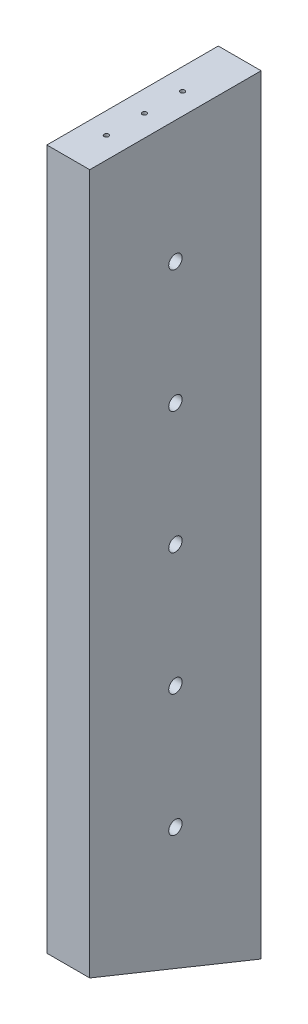
SolidWorks part; units mm, degrees
material "MDF"
ref_plane "Front" through (0, 0, 0) normal (0, 0, 1) x (1, 0, 0)
ref_plane "Top" through (0, 0, 0) normal (0, 1, 0) x (1, 0, 0)
ref_plane "Right" through (0, 0, 0) normal (1, 0, 0) x (0, 0, -1)
sketch "Sketch1" plane through (0, 0, 0) normal (0, 0, 1) x (1, 0, 0)
  line L0 (505.9785, 6983.73) -> (266.7, 6983.73) construction
  line L1 (494.5273, 6641.7419) -> (475.4773, 6641.7419)
  line L2 (494.5273, 6641.7419) -> (494.5273, 6983.73)
  line L3 (494.5273, 6983.73) -> (475.4773, 6983.73)
  line L4 (475.4773, 6641.7419) -> (475.4773, 6983.73)
  dimension "D1" = 19.05
extrude "Boss-Extrude1" add sketch "Sketch1" along normal blind 76.2
sketch "Sketch2" plane through (494.5273, 0, 0) normal (1, 0, 0) x (0, 0, -1)
  line L0 (0, 6641.7419) -> (-76.2, 6672.5287)
  line L1 (-76.2, 6641.7419) -> (-76.2, 6983.73) construction
  line L2 (-76.2, 6672.5287) -> (-76.2, 6641.7419)
  line L3 (-76.2, 6641.7419) -> (0, 6641.7419)
  line L5 (-110.6161, 6686.4337) -> (-134.1666, 6695.9487) construction
extrude "Cut-Extrude1" cut sketch "Sketch2" against normal up to next
hole_wizard "5/64 (0.07813) Diameter Hole1" positions "Sketch3" profile "Sketch4" hole size "5/64" standard "ANSI Inch"
sketch "Sketch3" plane through (0, 0, -19.05) normal (0, 0, -1) x (-1, 0, 0)
  point P0 (-481.5892, 6993.255)
  point P9 (-386.3392, 6993.255)
  point P18 (-291.0892, 6993.255)
  point P21 (-295.275, 6965.1359)
  point P33 (-295.275, 6812.7359)
  point P45 (-295.275, 6660.3359)
  point P48 (-285.1664, 6631.4688)
  point P66 (-475.4773, 6631.4688)
  point P69 (-485.0023, 6660.3359)
  point P81 (-485.0023, 6812.7359)
  point P93 (-485.0023, 6965.1359)
  point P96 (-478.3656, 6611.6708)
  point P114 (-287.8656, 6611.6708)
  point P117 (-307.975, 6564.3379)
  point P127 (-307.975, 6488.1379)
  point P130 (-284.9609, 6440.805)
  point P143 (-380.2109, 6440.805)
  point P152 (-475.4609, 6440.805)
  point P155 (-446.8313, 6488.1379)
  point P161 (-446.8313, 6564.3379)
  point P164 (-472.2313, 6396.355)
  point P170 (-472.2313, 6320.155)
  point P173 (-472.6532, 6275.705)
  point P182 (-377.4032, 6275.705)
  point P191 (-282.1532, 6275.705)
  point P194 (-282.575, 6320.155)
  point P200 (-282.575, 6396.355)
  point P203 (-435.5986, 6221.73)
  point P209 (-435.5986, 6145.53)
  point P233 (-450.5925, 6091.555)
  point P242 (-460.9986, 6091.5555)
  point P245 (-460.9986, 6056.63)
  point P251 (-460.9986, 5980.43)
  point P263 (-460.9986, 5945.505)
  point P280 (-282.1532, 5945.505)
  point P284 (-368.6118, 5945.505)
sketch "Sketch4" plane through (481.5892, 6993.255, -19.05) normal (1, 0, 0) x (0, 1, 0)
  line L0 (0, 0) -> (0, 38.6962)
  line L1 (0, 38.6962) -> (0.9923, 38.1)
  line L2 (0.9923, 38.1) -> (0.9923, 0)
  line L3 (0.9923, 0) -> (0, 0)
  line L4 (0, 38.6962) -> (-0.9923, 38.1) construction
  line L5 (0, -6.35) -> (0, 107.95) construction
  dimension "Hole Dia." = 1.9845
  dimension "Hole Depth" = 38.1
  dimension "Drill Angle" = 118
hole_wizard "5/64 (0.07813) Diameter Hole2" positions "Sketch5" profile "Sketch6" hole size "5/64" standard "ANSI Inch"
sketch "Sketch5" plane through (189.7273, 0, -19.05) normal (0, 0, -1) x (-1, 0, 0)
  point P0 (-481.5892, 6993.255)
  point P9 (-386.3392, 6993.255)
  point P18 (-291.0892, 6993.255)
  point P21 (-295.275, 6965.1359)
  point P33 (-295.275, 6812.7359)
  point P45 (-295.275, 6660.3359)
  point P48 (-285.1664, 6631.4688)
  point P66 (-475.4773, 6631.4688)
  point P69 (-485.0023, 6660.3359)
  point P81 (-485.0023, 6812.7359)
  point P93 (-485.0023, 6965.1359)
  point P96 (-478.3656, 6611.6708)
  point P114 (-287.8656, 6611.6708)
  point P117 (-307.975, 6564.3379)
  point P127 (-307.975, 6488.1379)
  point P130 (-284.9609, 6440.805)
  point P143 (-380.2109, 6440.805)
  point P152 (-475.4609, 6440.805)
  point P155 (-446.8313, 6488.1379)
  point P161 (-446.8313, 6564.3379)
  point P164 (-472.2313, 6396.355)
  point P170 (-472.2313, 6320.155)
  point P173 (-472.6532, 6275.705)
  point P182 (-377.4032, 6275.705)
  point P191 (-282.1532, 6275.705)
  point P194 (-282.575, 6320.155)
  point P200 (-282.575, 6396.355)
  point P203 (-435.5986, 6221.73)
  point P209 (-435.5986, 6145.53)
  point P233 (-450.5925, 6091.555)
  point P242 (-460.9986, 6091.5555)
  point P245 (-460.9986, 6056.63)
  point P251 (-460.9986, 5980.43)
  point P263 (-460.9986, 5945.505)
  point P280 (-282.1532, 5945.505)
  point P284 (-368.6118, 5945.505)
sketch "Sketch6" plane through (671.3166, 6993.255, -19.05) normal (1, 0, 0) x (0, 1, 0)
  line L0 (0, 0) -> (0, 38.6962)
  line L1 (0, 38.6962) -> (0.9923, 38.1)
  line L2 (0.9923, 38.1) -> (0.9923, 0)
  line L3 (0.9923, 0) -> (0, 0)
  line L4 (0, 38.6962) -> (-0.9923, 38.1) construction
  line L5 (0, -6.35) -> (0, 107.95) construction
  dimension "Hole Dia." = 1.9845
  dimension "Hole Depth" = 38.1
  dimension "Drill Angle" = 118
hole_wizard "5/64 (0.07813) Diameter Hole3" positions "Sketch7" profile "Sketch8" hole size "5/64" standard "ANSI Inch"
sketch "Sketch7" plane through (0, 6983.73, 0) normal (0, 1, 0) x (1, 0, 0)
  line L0 (485.0023, -76.2) -> (485.0023, 0) construction
  line L1 (494.5273, -76.2) -> (475.4773, -76.2) construction
  line L2 (494.5273, 0) -> (475.4773, 0) construction
  line L3 (485.0023, -25.4) -> (485.0023, -42.3333)
  line L4 (485.0023, -42.3333) -> (485.0023, -59.2667)
  line L5 (485.0023, -59.2667) -> (485.0023, -76.2)
  point P8 (485.0023, -25.4)
  point P10 (485.0023, -42.3333)
  point P12 (485.0023, -59.2667)
  dimension "D1" = 25.4
sketch "Sketch8" plane through (485.0023, 6983.73, 59.2667) normal (1, 0, 0) x (0, 0, 1)
  line L0 (0, 0) -> (0, 19.6462)
  line L1 (0, 19.6462) -> (0.9923, 19.05)
  line L2 (0.9923, 19.05) -> (0.9923, 0)
  line L5 (0.9923, 0) -> (0, 0)
  line L10 (0, 19.6462) -> (-0.9923, 19.05) construction
  line L11 (0, -6.35) -> (0, 107.95) construction
  dimension "Hole Dia." = 1.9845
  dimension "Hole Depth" = 19.05
  dimension "Drill Angle" = 118
hole_wizard "5/64 (0.07813) Diameter Hole4" positions "Sketch11" profile "Sketch10" hole size "5/64" standard "ANSI Inch"
sketch "Sketch11" plane through (0, 5709.7056, -2306.8708) normal (0, -0.9272, 0.3746) x (-1, 0, 0)
  line L0 (-485.0023, -2570.2247) -> (-485.0023, -2553.4132) construction
  line L1 (-475.4773, -2570.2247) -> (-494.5273, -2570.2247) construction
  line L2 (-485.0023, -2553.4132) -> (-485.0023, -2536.6018) construction
  line L3 (-485.0023, -2536.6018) -> (-485.0023, -2519.7903) construction
  line L4 (-485.0023, -2519.7903) -> (-485.0023, -2488.0403) construction
  line L5 (-475.4773, -2488.0403) -> (-494.5273, -2488.0403) construction
  point P2 (-485.0023, -2553.4132)
  point P6 (-485.0023, -2536.6018)
  point P8 (-485.0023, -2519.7903)
  dimension "D1" = 31.75
sketch "Sketch10" plane through (485.0023, 6653.6356, 29.4381) normal (1, 0, 0) x (0, -0.3746, -0.9272)
  line L0 (0, 0) -> (0, 19.6462)
  line L1 (0, 19.6462) -> (0.9923, 19.05)
  line L2 (0.9923, 19.05) -> (0.9923, 0)
  line L5 (0.9923, 0) -> (0, 0)
  line L10 (0, 19.6462) -> (-0.9923, 19.05) construction
  line L11 (0, -6.35) -> (0, 107.95) construction
  dimension "Hole Dia." = 1.9845
  dimension "Hole Depth" = 19.05
  dimension "Drill Angle" = 118
hole_wizard "15/64 (0.23438) Diameter Hole1" positions "Sketch14" profile "Sketch15" hole size "15/64" standard "ANSI Inch" end condition up to next
sketch "Sketch14" plane through (475.4773, 0, 0) normal (-1, 0, 0) x (0, 0, 1)
  line L0 (38.1, 6983.73) -> (38.1, 6657.1353) construction
  line L1 (76.2, 6983.73) -> (0, 6983.73) construction
  line L2 (76.2, 6672.5287) -> (0, 6641.7419) construction
  line L4 (76.2, 6983.73) -> (76.2, 6672.5287) construction
  line L5 (0, 6983.73) -> (0, 6641.7419) construction
  line L6 (38.1, 6983.73) -> (38.1, 6929.2975)
  line L7 (38.1, 6929.2975) -> (38.1, 6874.8651)
  line L8 (38.1, 6874.8651) -> (38.1, 6820.4326)
  line L9 (38.1, 6820.4326) -> (38.1, 6766.0002)
  line L10 (38.1, 6766.0002) -> (38.1, 6711.5677)
  line L11 (38.1, 6711.5677) -> (38.1, 6657.1353)
  point P15 (38.1, 6929.2975)
  point P17 (38.1, 6874.8651)
  point P19 (38.1, 6820.4326)
  point P21 (38.1, 6766.0002)
  point P22 (38.1, 6711.5677)
  dimension "D1" = 38.1
sketch "Sketch15" plane through (475.4773, 6711.5677, 38.1) normal (0, 1, 0) x (0, 0, 1)
  line L0 (0, 0) -> (0, 19.05)
  line L1 (0, 19.05) -> (2.9766, 19.05)
  line L2 (2.9766, 19.05) -> (2.9766, 0)
  line L5 (2.9766, 0) -> (0, 0)
  line L11 (0, -6.35) -> (0, 107.95) construction
  dimension "Thru Hole Dia." = 5.9533
  dimension "Thru Hole Depth" = 19.05
